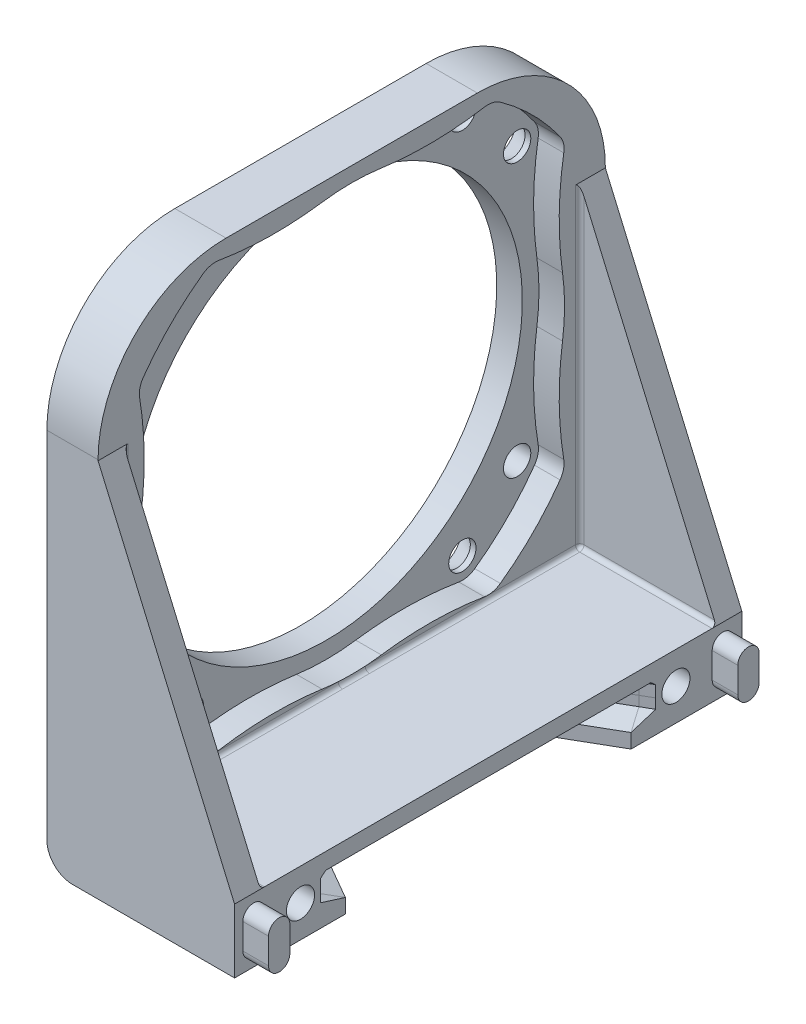
SolidWorks part; units mm, degrees
material "6061 合金"
ref_plane "前视基准面" through (0, 0, 0) normal (0, 0, 1) x (1, 0, 0)
ref_plane "上视基准面" through (0, 0, 0) normal (0, 1, 0) x (1, 0, 0)
ref_plane "右视基准面" through (0, 0, 0) normal (1, 0, 0) x (0, 0, -1)
other "Configuration Table"
sketch "草图1" plane through (0, 0, 0) normal (0, 1, 0) x (1, 0, 0)
  line L0 (0, 16.7432) -> (0, 29.7252)
  line L1 (0, 16.7432) -> (-14.5, 8.3716)
  line L2 (-14.5, 8.3716) -> (-14.5, -8.3716)
  line L3 (-14.5, -8.3716) -> (0, -16.7432)
  line L4 (0, -16.7432) -> (14.5, -8.3716) construction
  line L5 (14.5, -8.3716) -> (14.5, 8.3716) construction
  line L6 (14.5, 8.3716) -> (0, 16.7432) construction
  line L7 (0, 29.7252) -> (-22, 29.7252)
  line L8 (-22, 29.7252) -> (-22, -29.7252)
  line L9 (-22, -29.7252) -> (0, -29.7252)
  line L10 (0, -29.7252) -> (0, -16.7432)
  line L11 (-22, 0) -> (14.5, 0) construction
  circle A0 centre (0, 0) radius 14.5 construction
  dimension "D1" = 29
  dimension "D2" = 59.4504
  dimension "D3" = 22
extrude "凸台-拉伸1" add sketch "草图1" along normal blind 7.5
ref_plane "基准面3" through (12.8714, 0, 7.4313) normal (0.866, 0, 0.5) x (0, -1, 0)
sketch "草图2" plane through (-16.7286, 0, 58.7) normal (-0.866, 0, -0.5) x (-0.5, 0, 0.866)
  line L0 (-33.4573, 3.75) -> (-84.9428, 3.75) construction
  line L1 (-33.4573, 7.5) -> (-33.4573, 0) construction
  line L2 (-84.9428, 7.5) -> (-84.9428, 0) construction
  line L4 (-42.2, 3.75) -> (-42.2, 5.5919)
  line L8 (-44.7, 1.682) -> (-44.7, 3.75)
  line L10 (-42.2, 3.75) -> (-42.2, 2.5919)
  line L11 (-44.7, 1.682) -> (-42.2, 2.5919)
  line L12 (-44.7, 7.5) -> (-44.7, 0) construction
  line L13 (-42.2, 5.5919) -> (-44.7, 5.5919)
  line L14 (-44.7, 5.5919) -> (-44.7, 3.75)
  point P11 (-40.2, 3.75)
  point P12 (-43.7746, 3.75)
  dimension "D1" = 1.1581
  dimension "D2" = 2.5
  dimension "D3" = 20
  dimension "D4" = 3
ref_plane "基准面1" through (0, 3.75, 0) normal (0, 1, 0) x (1, 0, 0)
sketch "草图3" plane through (0, 3.75, 0) normal (0, 1, 0) x (1, 0, 0)
  line L0 (0, -16.7432) -> (-14.5, -8.3716) construction
  line L1 (-14.5, 8.3716) -> (0, 16.7432) construction
  line L2 (-14.5, -8.3716) -> (-14.5, 8.3716) construction
  line L3 (0, -16.7432) -> (-14.5, -8.3716)
  line L4 (-14.5, 8.3716) -> (0, 16.7432)
  line L5 (-14.5, -8.3716) -> (-14.5, 8.3716)
  line L6 (0, 16.7432) -> (15.4317, 25.6527)
  line L7 (0, -16.7432) -> (15.5318, -25.7104)
sweep "切除-扫描1" cut profiles "草图2" path "草图3"
fillet "圆角1" radius 5 4 edges at (-17, 3.171, -9.815) (-17, 3.171, 9.815) (-17, 4.671, -9.815) (-17, 4.671, 9.815)
fillet "圆角2" radius 1 4 edges at (-14.5, 0.841, -8.3716) (-14.5, 6.546, -8.3716) (-14.5, 0.841, 8.3716) (-14.5, 6.546, 8.3716)
sketch "草图4" plane through (0, 7.5, 0) normal (0, 1, 0) x (1, 0, 0)
  line L0 (-22, -29.7252) -> (0, -29.7252) construction
  line L1 (-22, 29.7252) -> (-19, 29.7252)
  line L2 (-22, 29.7252) -> (-22, -29.7252)
  line L3 (-22, -29.7252) -> (-19, -29.7252)
  line L4 (-19, 29.7252) -> (-19, -29.7252)
  dimension "D1" = 3
extrude "凸台-拉伸2" add sketch "草图4" along normal blind 55.6
sketch "草图5" plane through (-22, 0, 0) normal (-1, 0, 0) x (0, 0, 1)
  line L0 (-29.7252, 0) -> (29.7252, 0) construction
  line L1 (-27.5, 32.9) -> (0, 32.9) construction
  line L2 (-22.3882, 48.8693) -> (0, 32.9) construction
  line L3 (-15.9693, 55.2882) -> (0, 32.9) construction
  circle A0 centre (0, 32.9) radius 27.5 construction
  circle A1 centre (-22.3882, 48.8693) radius 1.6
  circle A2 centre (-15.9693, 55.2882) radius 1.6
  circle A3 centre (15.9693, 55.2882) radius 1.6
  circle A4 centre (22.3882, 48.8693) radius 1.6
  circle A5 centre (22.3882, 16.9307) radius 1.6
  circle A6 centre (15.9693, 10.5118) radius 1.6
  circle A7 centre (-15.9693, 10.5118) radius 1.6
  circle A8 centre (-22.3882, 16.9307) radius 1.6
  circle A9 centre (0, 32.9) radius 23
  point P25 (0, 32.9)
  dimension "D2" = 55
  dimension "D5" = 3.2
  dimension "D6" = 3.2
  dimension "D8" = 46
  dimension "D1" = 32.9
  dimension "D3" = 35.5
  dimension "D4" = 19
  dimension "D7" = 4
extrude "切除-拉伸1" cut sketch "草图5" against normal blind 55.6
ref_axis "基准轴1" through (-19, 10.5118, -15.9693) along (-1, 0, 0)
ref_plane "基准面2" through (0, 0, -15.9693) normal (0, 0, 1) x (-1, 0, 0)
sketch "草图6" plane through (0, 0, -15.9693) normal (0, 0, 1) x (-1, 0, 0)
  line L0 (22, -10.5118) -> (22, -7.5118)
  line L1 (19, -10.5118) -> (22, -10.5118) construction
  line L2 (22, -7.5118) -> (19.5, -9.0118)
  line L3 (19.5, -9.0118) -> (19.5, -10.5118)
  line L5 (22, -63.1) -> (22, 0) construction
  line L6 (19.5, -10.5118) -> (22, -10.5118)
  dimension "D1" = 3
  dimension "D2" = 1.5
  dimension "D3" = 2.5
revolve "切除-旋转1" cut sketch "草图6" angle 360 about axis through (-19, 10.5118, -15.9693) along (-1, 0, 0)
pattern_circular "阵列(圆周)1" count 4 every 90 about axis through (33.6, 32.9, 0) along (-1, 0, 0) of "切除-旋转1"
sketch "草图7" plane through (-19, 0, 0) normal (1, 0, 0) x (0, 0, -1)
  line L16 (-29.7252, 7.5) -> (29.7252, 7.5)
  line L17 (29.7252, 7.5) -> (29.7252, 63.1)
  line L18 (29.7252, 63.1) -> (-29.7252, 63.1)
  line L19 (-29.7252, 63.1) -> (-29.7252, 7.5)
  line L20 (-29.7252, 7.5) -> (29.7252, 7.5)
  line L21 (29.7252, 7.5) -> (29.7252, 63.1)
  line L22 (29.7252, 63.1) -> (-29.7252, 63.1)
  line L23 (-29.7252, 63.1) -> (-29.7252, 7.5)
  arc A76 (-15.5614, 57.7547) -> (-3.4705, 57.6074) centre (-9.0345, 97.2186) ccw
  arc A77 (3.4705, 57.6074) -> (-3.4705, 57.6074) centre (0, 32.9) ccw
  arc A78 (3.4705, 57.6074) -> (15.5614, 57.7547) centre (9.0345, 97.2186) ccw
  arc A79 (17.4211, 57.3235) -> (15.5614, 57.7547) centre (15.9693, 55.2882) ccw
  arc A80 (24.4235, 50.3211) -> (17.4211, 57.3235) centre (0, 32.9) ccw
  arc A81 (24.8547, 48.4614) -> (24.4235, 50.3211) centre (22.3882, 48.8693) ccw
  arc A82 (24.8547, 48.4614) -> (24.7074, 36.3705) centre (64.3186, 41.9345) ccw
  arc A83 (24.7074, 29.4295) -> (24.7074, 36.3705) centre (0, 32.9) ccw
  arc A84 (24.7074, 29.4295) -> (24.8547, 17.3386) centre (64.3186, 23.8655) ccw
  arc A85 (24.4235, 15.4789) -> (24.8547, 17.3386) centre (22.3882, 16.9307) ccw
  arc A86 (17.4211, 8.4765) -> (24.4235, 15.4789) centre (0, 32.9) ccw
  arc A87 (15.5614, 8.0453) -> (17.4211, 8.4765) centre (15.9693, 10.5118) ccw
  arc A88 (15.5614, 8.0453) -> (3.4705, 8.1926) centre (9.0345, -31.4186) ccw
  arc A89 (-3.4705, 8.1926) -> (3.4705, 8.1926) centre (0, 32.9) ccw
  arc A90 (-3.4705, 8.1926) -> (-15.5614, 8.0453) centre (-9.0345, -31.4186) ccw
  arc A91 (-17.4211, 8.4765) -> (-15.5614, 8.0453) centre (-15.9693, 10.5118) ccw
  arc A92 (-24.4235, 15.4789) -> (-17.4211, 8.4765) centre (0, 32.9) ccw
  arc A93 (-24.8547, 17.3386) -> (-24.4235, 15.4789) centre (-22.3882, 16.9307) ccw
  arc A94 (-24.8547, 17.3386) -> (-24.7074, 29.4295) centre (-64.3186, 23.8655) ccw
  arc A95 (-24.7074, 36.3705) -> (-24.7074, 29.4295) centre (0, 32.9) ccw
  arc A96 (-24.7074, 36.3705) -> (-24.8547, 48.4614) centre (-64.3186, 41.9345) ccw
  arc A97 (-24.4235, 50.3211) -> (-24.8547, 48.4614) centre (-22.3882, 48.8693) ccw
  arc A98 (-17.4211, 57.3235) -> (-24.4235, 50.3211) centre (0, 32.9) ccw
  arc A99 (-15.5614, 57.7547) -> (-17.4211, 57.3235) centre (-15.9693, 55.2882) ccw
  arc A100 (-15.5614, 57.7547) -> (-3.4705, 57.6074) centre (-9.0345, 97.2186) ccw
  arc A101 (3.4705, 57.6074) -> (-3.4705, 57.6074) centre (0, 32.9) ccw
  arc A102 (3.4705, 57.6074) -> (15.5614, 57.7547) centre (9.0345, 97.2186) ccw
  arc A103 (17.4211, 57.3235) -> (15.5614, 57.7547) centre (15.9693, 55.2882) ccw
  arc A104 (24.4235, 50.3211) -> (17.4211, 57.3235) centre (0, 32.9) ccw
  arc A105 (24.8547, 48.4614) -> (24.4235, 50.3211) centre (22.3882, 48.8693) ccw
  arc A106 (24.8547, 48.4614) -> (24.7074, 36.3705) centre (64.3186, 41.9345) ccw
  arc A107 (24.7074, 29.4295) -> (24.7074, 36.3705) centre (0, 32.9) ccw
  arc A108 (24.7074, 29.4295) -> (24.8547, 17.3386) centre (64.3186, 23.8655) ccw
  arc A109 (24.4235, 15.4789) -> (24.8547, 17.3386) centre (22.3882, 16.9307) ccw
  arc A110 (17.4211, 8.4765) -> (24.4235, 15.4789) centre (0, 32.9) ccw
  arc A111 (15.5614, 8.0453) -> (17.4211, 8.4765) centre (15.9693, 10.5118) ccw
  arc A112 (15.5614, 8.0453) -> (3.4705, 8.1926) centre (9.0345, -31.4186) ccw
  arc A113 (-3.4705, 8.1926) -> (3.4705, 8.1926) centre (0, 32.9) ccw
  arc A114 (-3.4705, 8.1926) -> (-15.5614, 8.0453) centre (-9.0345, -31.4186) ccw
  arc A115 (-17.4211, 8.4765) -> (-15.5614, 8.0453) centre (-15.9693, 10.5118) ccw
  arc A116 (-24.4235, 15.4789) -> (-17.4211, 8.4765) centre (0, 32.9) ccw
  arc A117 (-24.8547, 17.3386) -> (-24.4235, 15.4789) centre (-22.3882, 16.9307) ccw
  arc A118 (-24.8547, 17.3386) -> (-24.7074, 29.4295) centre (-64.3186, 23.8655) ccw
  arc A119 (-24.7074, 36.3705) -> (-24.7074, 29.4295) centre (0, 32.9) ccw
  arc A120 (-24.7074, 36.3705) -> (-24.8547, 48.4614) centre (-64.3186, 41.9345) ccw
  arc A121 (-24.4235, 50.3211) -> (-24.8547, 48.4614) centre (-22.3882, 48.8693) ccw
  arc A122 (-17.4211, 57.3235) -> (-24.4235, 50.3211) centre (0, 32.9) ccw
  arc A123 (-15.5614, 57.7547) -> (-17.4211, 57.3235) centre (-15.9693, 55.2882) ccw
  dimension "D1" = 0
  dimension "D2" = 0
extrude "凸台-拉伸3" add sketch "草图7" along normal blind 3
sketch "草图8" plane through (0, 0, 0) normal (1, 0, 0) x (0, 0, -1)
  line L0 (-29.7252, 0) -> (-16.7432, 0) construction
  line L1 (-29.7252, 7.5) -> (-26.7252, 7.5)
  line L2 (-29.7252, 7.5) -> (-29.7252, 0)
  line L3 (-29.7252, 0) -> (-26.7252, 0)
  line L4 (-26.7252, 7.5) -> (-26.7252, 0)
  line L5 (16.7432, 0) -> (29.7252, 0) construction
  line L6 (29.7252, 7.5) -> (26.7252, 7.5)
  line L7 (29.7252, 7.5) -> (29.7252, 0)
  line L8 (29.7252, 0) -> (26.7252, 0)
  line L9 (26.7252, 7.5) -> (26.7252, 0)
  dimension "D1" = 3
  dimension "D2" = 3
extrude "凸台-拉伸4" add sketch "草图8" along normal blind 15
sketch "草图9" plane through (0, 0, 29.7252) normal (0, 0, 1) x (1, 0, 0)
  line L0 (-16, 51.1) -> (13, 7.5)
  line L1 (13, 7.5) -> (-16, 7.5)
  line L2 (-16, 7.5) -> (-16, 51.1)
  line L4 (-22, 63.1) -> (-16, 63.1) construction
  line L5 (-16, 7.5) -> (15, 7.5) construction
  line L7 (15, 7.5) -> (15, 0) construction
  dimension "D1" = 12
  dimension "D2" = 2
extrude "凸台-拉伸5" add sketch "草图9" against normal blind 3
sketch "草图10" plane through (0, 0, -29.7252) normal (0, 0, -1) x (-1, 0, 0)
  line L3 (16, 7.5) -> (16, 51.1)
  line L4 (16, 51.1) -> (-13, 7.5)
  line L5 (-13, 7.5) -> (-15, 7.5)
  line L7 (16, 51.1) -> (-13, 7.5)
  line L8 (-13, 7.5) -> (-15, 7.5)
  line L13 (0, 0) -> (0, 7.5)
  line L14 (0, 0) -> (0, 7.5)
  line L15 (0, 7.5) -> (16, 7.5)
  line L16 (0, 7.5) -> (16, 7.5)
  line L17 (-15, 7.5) -> (-15, 0)
  line L18 (-15, 7.5) -> (-15, 0)
  line L19 (-15, 0) -> (0, 0)
  line L20 (-15, 0) -> (0, 0)
  line L23 (16, 7.5) -> (16, 51.1)
  dimension "D1" = 0
extrude "凸台-拉伸6" add sketch "草图10" against normal blind 3
sketch "草图12" plane through (0, 0, 0) normal (1, 0, 0) x (0, 0, -1)
  line L0 (10.45, 3.75) -> (-10.45, 3.75) construction
  line L1 (0, 0) -> (0, 6) construction
  point P0 (-22, 3.75)
  point P4 (22, 3.75)
  dimension "D1" = 44
hole_wizard "M4 螺纹孔1" positions "草图12" profile "草图13" tap size "M4" standard "GB"
sketch "草图13" plane through (0, 3.75, 22) normal (0, 1, 0) x (0, 0, -1)
  line L0 (0, 0) -> (0, 6.4914)
  line L1 (0, 6.4914) -> (1.65, 5.5)
  line L2 (1.65, 5.5) -> (1.65, 0)
  line L5 (1.65, 0) -> (0, 0)
  line L10 (0, 6.4914) -> (-1.65, 5.5) construction
  line L11 (0, -6.35) -> (0, 107.95) construction
  dimension "螺纹孔钻头直径" = 3.3
  dimension "螺纹孔钻头深度" = 5.5
  dimension "导头角度" = 118
cosmetic thread "孔螺蚊线1" parameters "D1"=4, "D2"=4
cosmetic thread "孔螺蚊线2" parameters "D1"=4, "D2"=4
sketch "草图14" plane through (15, 0, 0) normal (1, 0, 0) x (0, 0, -1)
  line L0 (-28.2252, 7.5) -> (-28.2252, 0) construction
  line L1 (-26.7252, 7.5) -> (-29.7252, 7.5) construction
  line L2 (-29.7252, 0) -> (-26.7252, 0) construction
  line L3 (-29.7252, 3.75) -> (29.7252, 3.75) construction
  line L4 (-29.7252, 7.5) -> (-29.7252, 0) construction
  line L5 (29.7252, 0) -> (29.7252, 7.5) construction
  line L6 (0, 0) -> (0, 6) construction
  line L8 (-28.2252, 5.75) -> (-28.2252, 1.75) construction
  line L9 (-27.4752, 5.75) -> (-27.4752, 1.75)
  line L10 (-28.9752, 5.75) -> (-28.9752, 1.75)
  line L11 (28.2252, 5.75) -> (28.2252, 1.75) construction
  line L12 (27.4752, 5.75) -> (27.4752, 1.75)
  line L13 (28.9752, 5.75) -> (28.9752, 1.75)
  arc A2 (-27.4752, 5.75) -> (-28.9752, 5.75) centre (-28.2252, 5.75) ccw
  arc A3 (-28.9752, 1.75) -> (-27.4752, 1.75) centre (-28.2252, 1.75) ccw
  arc A4 (27.4752, 5.75) -> (28.9752, 5.75) centre (28.2252, 5.75) cw
  arc A5 (28.9752, 1.75) -> (27.4752, 1.75) centre (28.2252, 1.75) cw
  point P19 (-28.2252, 3.75)
  point P27 (28.2252, 3.75)
  dimension "D1" = 1.5
  dimension "D2" = 4
extrude "切除-拉伸2" cut sketch "草图14" against normal blind 5.2
sketch "草图17" plane through (0, 0, 0) normal (0, -1, 0) x (1, 0, 0)
  line L0 (0, 26.7252) -> (0, 16.7432) construction
  line L1 (0, 16.7432) -> (-14, 8.6603) construction
  line L2 (-14.5, 7.7942) -> (-14.5, -7.7942) construction
  line L3 (0, -16.7432) -> (0, -26.7252) construction
  line L4 (-14, -8.6603) -> (0, -16.7432) construction
  line L5 (0, -16.7432) -> (0, -26.7252)
  line L6 (-14, -8.6603) -> (0, -16.7432)
  line L7 (-14.5, 7.7942) -> (-14.5, -7.7942)
  line L8 (0, 16.7432) -> (-14, 8.6603)
  line L9 (0, 26.7252) -> (0, 16.7432)
  circle A0 centre (0, 0) radius 22.95
  arc A1 (-14.5, -7.7942) -> (-14, -8.6603) centre (-13.5, -7.7942) ccw construction
  arc A2 (-14, 8.6603) -> (-14.5, 7.7942) centre (-13.5, 7.7942) ccw construction
  arc A3 (-14.5, -7.7942) -> (-14, -8.6603) centre (-13.5, -7.7942) ccw
  arc A4 (-14, 8.6603) -> (-14.5, 7.7942) centre (-13.5, 7.7942) ccw
  dimension "D1" = 45.9
sketch "草图28" plane through (-22, 0, 0) normal (-1, 0, 0) x (0, 0, 1)
  line L0 (29.7252, 63.1) -> (29.7252, 0) construction
  line L1 (-29.7252, 63.1) -> (29.7252, 63.1)
  line L2 (-29.7252, 63.1) -> (-29.7252, 59.6)
  line L3 (-29.7252, 59.6) -> (29.7252, 59.6)
  line L4 (29.7252, 63.1) -> (29.7252, 59.6)
  dimension "D1" = 3.5
extrude "切除-拉伸7" cut sketch "草图28" against normal blind 10
fillet "圆角5" radius 15 2 edges at (-19, 59.6, -29.7252) (-19, 59.6, 29.7252)
chamfer "倒角2" distance 0.5 angle 45 4 edges at (15, 3.75, -29.7252) (15, 3.75, -26.7252) (15, 3.75, 26.7252) (15, 3.75, 29.7252)
sketch "草图21" plane through (0, 0, 26.7252) normal (0, 0, -1) x (-1, 0, 0)
  line L0 (-14.5, 0) -> (-15, 0)
  line L1 (-15, 0) -> (-15, 7.5)
  line L2 (-15, 7.5) -> (-14.5, 7.5)
  line L7 (-13, 7.5) -> (-14.5, 7.5)
  line L8 (-14.5, 7.5) -> (-14.5, 0)
  line L9 (-14.5, 0) -> (0, 0)
  line L10 (0, 0) -> (0, 7.5)
  line L11 (0, 7.5) -> (16, 7.5)
  line L12 (0, 7.5) -> (16, 7.5)
  line L13 (16, 51.1) -> (-13, 7.5)
  line L14 (-13, 7.5) -> (-14.5, 7.5)
  line L16 (-14.5, 0) -> (0, 0)
  line L20 (16, 51.1) -> (-13, 7.5)
  line L24 (0, 0) -> (0, 7.5)
  line L25 (16, 7.5) -> (16, 51.1)
  line L28 (16, 7.5) -> (16, 51.1)
  dimension "D1" = 0
extrude "切除-拉伸5" cut sketch "草图21" against normal through all and the other way through all
sketch "草图22" plane through (0, 0, 29.7252) normal (0, 0, 1) x (1, 0, 0)
  line L0 (0, 7.5) -> (-16, 44.5)
  line L2 (-16, 44.5) -> (-16, 7.5)
  line L3 (-16, 7.5) -> (0, 7.5)
  dimension "D1" = 37
extrude "凸台-拉伸8" add sketch "草图22" against normal blind 3
sketch "草图23" plane through (0, 0, -29.7252) normal (0, 0, -1) x (-1, 0, 0)
  line L3 (0, 7.5) -> (16, 7.5)
  line L4 (16, 7.5) -> (16, 44.5)
  line L5 (16, 44.5) -> (0, 7.5)
  line L6 (0, 7.5) -> (16, 7.5)
  line L8 (16, 44.5) -> (0, 7.5)
  line L11 (16, 7.5) -> (16, 44.5)
  dimension "D1" = 0
extrude "凸台-拉伸9" add sketch "草图23" against normal blind 3
sketch "草图24" plane through (0, 0, 0) normal (1, 0, 0) x (0, 0, -1)
  line L0 (-29.7252, 3.75) -> (29.7252, 3.75) construction
  line L1 (-29.7252, 0) -> (-29.7252, 7.5) construction
  line L2 (29.7252, 0) -> (29.7252, 7.5) construction
  line L3 (0, 0) -> (0, 7.95) construction
  line L4 (-27.5, 5.25) -> (-27.5, 2.25) construction
  line L5 (-26.25, 5.25) -> (-26.25, 2.25)
  line L6 (-28.75, 5.25) -> (-28.75, 2.25)
  line L7 (27.5, 5.25) -> (27.5, 2.25) construction
  line L8 (26.25, 5.25) -> (26.25, 2.25)
  line L9 (28.75, 5.25) -> (28.75, 2.25)
  arc A3 (-26.25, 5.25) -> (-28.75, 5.25) centre (-27.5, 5.25) ccw
  arc A4 (-28.75, 2.25) -> (-26.25, 2.25) centre (-27.5, 2.25) ccw
  arc A5 (26.25, 5.25) -> (28.75, 5.25) centre (27.5, 5.25) cw
  arc A6 (28.75, 2.25) -> (26.25, 2.25) centre (27.5, 2.25) cw
  point P14 (-27.5, 3.75)
  point P22 (27.5, 3.75)
  dimension "D1" = 27.5
  dimension "D2" = 3
  dimension "D3" = 2.5
extrude "切除-拉伸6" cut sketch "草图24" against normal blind 3.2
chamfer "倒角3" distance 0.5 angle 45 9 edges at (-0.625, 5.5919, 19.2691) (-7.875, 5.5919, 15.0833) (-15.5355, 5.5919, 10.4637) (-16.8296, 5.5919, 8.2223) (-17, 5.5919, 0) (-16.8296, 5.5919, -8.2223) (-0.625, 5.5919, -19.2691) (-15.5355, 5.5919, -10.4637) (-7.875, 5.5919, -15.0833)
sketch "草图25" plane through (0, 7.5, 0) normal (0, 1, 0) x (1, 0, 0)
  line L0 (-14, 8.6603) -> (0, 16.7432) construction
  line L1 (0, -16.7432) -> (-14, -8.6603) construction
  line L2 (-14, 8.6603) -> (0, 16.7432)
  line L3 (0, -16.7432) -> (-14, -8.6603)
  line L4 (0, 16.7432) -> (0, -16.7432)
  line L5 (-14.5, 7.7942) -> (-14.5, -7.7942)
  arc A0 (-14, 8.6603) -> (-14.5, 7.7942) centre (-13.5, 7.7942) ccw construction
  arc A1 (-14.5, -7.7942) -> (-14, -8.6603) centre (-13.5, -7.7942) ccw construction
  arc A2 (-14.5, -7.7942) -> (-14, -8.6603) centre (-13.5, -7.7942) ccw
  arc A3 (-14, 8.6603) -> (-14.5, 7.7942) centre (-13.5, 7.7942) ccw
extrude "凸台-拉伸10" add sketch "草图25" against normal up to surface (1.9081 mm away) up to face at (-9.9409, 5.5919, -12.0515)
fillet "圆角6" radius 3 1 edges at (-22, 0, 0)
fillet "圆角7" radius 0.5 5 edges at (-8, 7.5, -26.7252) (-8, 7.5, 26.7252) (-16, 7.5, 0) (-16, 26, -26.7252) (-16, 26, 26.7252)
sketch "草图27" plane through (-3.2, 0, 0) normal (1, 0, 0) x (0, 0, -1)
  line L0 (26.25, 5.25) -> (26.25, 2.25) construction
  line L1 (28.75, 2.25) -> (28.75, 5.25) construction
  line L2 (-28.75, 5.25) -> (-28.75, 2.25) construction
  line L3 (-26.25, 2.25) -> (-26.25, 5.25) construction
  line L4 (26.25, 5.25) -> (26.25, 2.25)
  line L5 (28.75, 2.25) -> (28.75, 5.25)
  line L6 (-28.75, 5.25) -> (-28.75, 2.25)
  line L7 (-26.25, 2.25) -> (-26.25, 5.25)
  arc A0 (28.75, 5.25) -> (26.25, 5.25) centre (27.5, 5.25) ccw construction
  arc A1 (26.25, 2.25) -> (28.75, 2.25) centre (27.5, 2.25) ccw construction
  arc A2 (-26.25, 5.25) -> (-28.75, 5.25) centre (-27.5, 5.25) ccw construction
  arc A3 (-28.75, 2.25) -> (-26.25, 2.25) centre (-27.5, 2.25) ccw construction
  arc A4 (28.75, 5.25) -> (26.25, 5.25) centre (27.5, 5.25) ccw
  arc A5 (26.25, 2.25) -> (28.75, 2.25) centre (27.5, 2.25) ccw
  arc A6 (-26.25, 5.25) -> (-28.75, 5.25) centre (-27.5, 5.25) ccw
  arc A7 (-28.75, 2.25) -> (-26.25, 2.25) centre (-27.5, 2.25) ccw
extrude "凸台-拉伸11" add sketch "草图27" along normal blind 6.2
